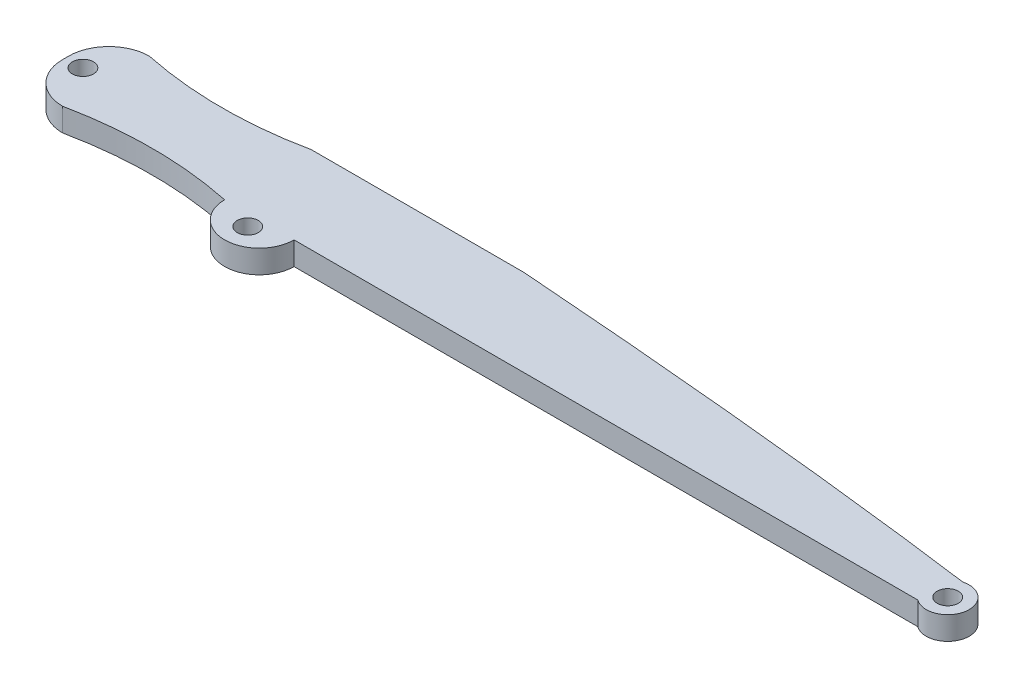
SolidWorks part; units mm, degrees
ref_plane "Front Plane" through (0, 0, 0) normal (0, 0, 1) x (1, 0, 0)
ref_plane "Top Plane" through (0, 0, 0) normal (0, 1, 0) x (1, 0, 0)
ref_plane "Right Plane" through (0, 0, 0) normal (1, 0, 0) x (0, 0, -1)
sketch "Sketch2" plane through (0, 0, 0) normal (0, 1, 0) x (1, 0, 0)
  line L11 (-80, 7.5) -> (80, 7.5)
  line L12 (-80, 7.5) -> (-80, -7.5)
  line L13 (-80, -7.5) -> (80, -7.5)
  line L14 (80, 7.5) -> (80, -7.5)
  dimension "D2" = 80
  dimension "D1" = 160
  dimension "D3" = 15
  dimension "D4" = 7.5
extrude "Boss-Extrude1" add sketch "Sketch2" along normal blind 4
sketch "Sketch4" plane through (0, 0, 0) normal (0, 1, 0) x (1, 0, 0)
  line L0 (-80, -7.5) -> (80, -7.5) construction
  line L1 (-45, -7.5) -> (-33, -7.5)
  arc A0 (-45, -7.5) -> (-33, -7.5) centre (-39, -7.5) ccw
  dimension "D1" = 6
  dimension "D2" = 35
  dimension "D3" = 12
extrude "Boss-Extrude2" add sketch "Sketch4" along normal up to surface (4 mm away) up to face at (0, 4, 0)
sketch "Sketch5" plane through (0, 4, 0) normal (0, 1, 0) x (1, 0, 0)
  line L0 (-80, -7.5) -> (-45, -7.5) construction
  line L1 (-80, 7.5) -> (-80, -7.5) construction
  line L2 (80, -7.5) -> (80, 7.5) construction
  line L3 (-33, -7.5) -> (80, -7.5) construction
  circle A0 centre (-77, 0) radius 1.825
  circle A1 centre (-39, -9.5) radius 1.825
  circle A2 centre (77, -4.5) radius 1.825
  arc A3 (-45, -7.5) -> (-33, -7.5) centre (-39, -7.5) ccw construction
  point P10 (-39, -13.5)
  dimension "D1" = 3.65
  dimension "D2" = 3.65
  dimension "D3" = 3.65
  dimension "D4" = 6
  dimension "D5" = 4
  dimension "D6" = 7.5
  dimension "D7" = 3
  dimension "D8" = 3
  dimension "D9" = 3
extrude "Cut-Extrude1" cut sketch "Sketch5" against normal through all
sketch "Sketch6" plane through (0, 4, 0) normal (0, 1, 0) x (1, 0, 0)
  line L2 (80, 7.5) -> (-8.2315, 7.5)
  line L3 (80, 7.5) -> (-80, 7.5) construction
  line L6 (-8.2315, 7.5) -> (14.2901, 5.8703) construction
  line L7 (14.2901, 5.8703) -> (49.5381, 2.8486) construction
  line L8 (49.5381, 2.8486) -> (69.508, -0.0694) construction
  line L9 (69.508, -0.0694) -> (80, -1.4494) construction
  line L10 (80, -7.5) -> (80, 7.5) construction
  line L11 (80, -1.4494) -> (80, 7.5)
  spline S0 degree 4 poles (-8.2315, 7.5) (14.2901, 5.8703) (49.5381, 2.8486) (69.508, -0.0694) (80, -1.4494) knots 0 0 0 0 0 1 1 1 1 1
  dimension "D1" = 88.6991
  dimension "D8" = 1.6297
  dimension "D2" = 88.2315
  dimension "D3" = 8.9494
  dimension "D4" = 10.5824
  dimension "D5" = 19.9699
  dimension "D6" = 22.5216
  dimension "D7" = 35.248
extrude "Cut-Extrude2" cut sketch "Sketch6" against normal through all
fillet "Fillet1" radius 7 2 edges at (-80, 2, -7.5) (-80, 2, 7.5)
fillet "Fillet2" radius 2 3 edges at (-8.2315, 2, -7.5) (80, 2, 7.5) (80, 2, 1.4494)
sketch "Sketch7" plane through (0, 4, 0) normal (0, 1, 0) x (1, 0, 0)
  line L0 (-73, -7.5) -> (-45, -7.5)
  line L1 (-73, -7.5) -> (-45, -7.5) construction
  line L2 (-73, 7.5) -> (-45, 7.5)
  line L3 (-8.3038, 7.5) -> (-73, 7.5) construction
  arc A1 (-45, -7.5) -> (-73, -7.5) centre (-59, -74.1454) ccw
  arc A2 (-73, 7.5) -> (-45, 7.5) centre (-59, 74.1454) ccw
  dimension "D1" = 68.1
  dimension "D2" = 28
  dimension "D3" = 68.1
extrude "Cut-Extrude3" cut sketch "Sketch7" against normal through all
sketch "Sketch8" plane through (0, 4, 0) normal (0, 1, 0) x (1, 0, 0)
  circle A0 centre (77, -4.5) radius 3.7056
  dimension "D1" = 7.4112
extrude "Boss-Extrude4" add sketch "Sketch8" against normal up to surface (4 mm away) up to face at (-77, 0, 1.825)
sketch "Sketch9" plane through (0, 4, 0) normal (0, 1, 0) x (1, 0, 0)
  circle A2 centre (77, -4.5) radius 1.825
  dimension "D1" = 3.65
extrude "Cut-Extrude4" cut sketch "Sketch9" against normal through all
